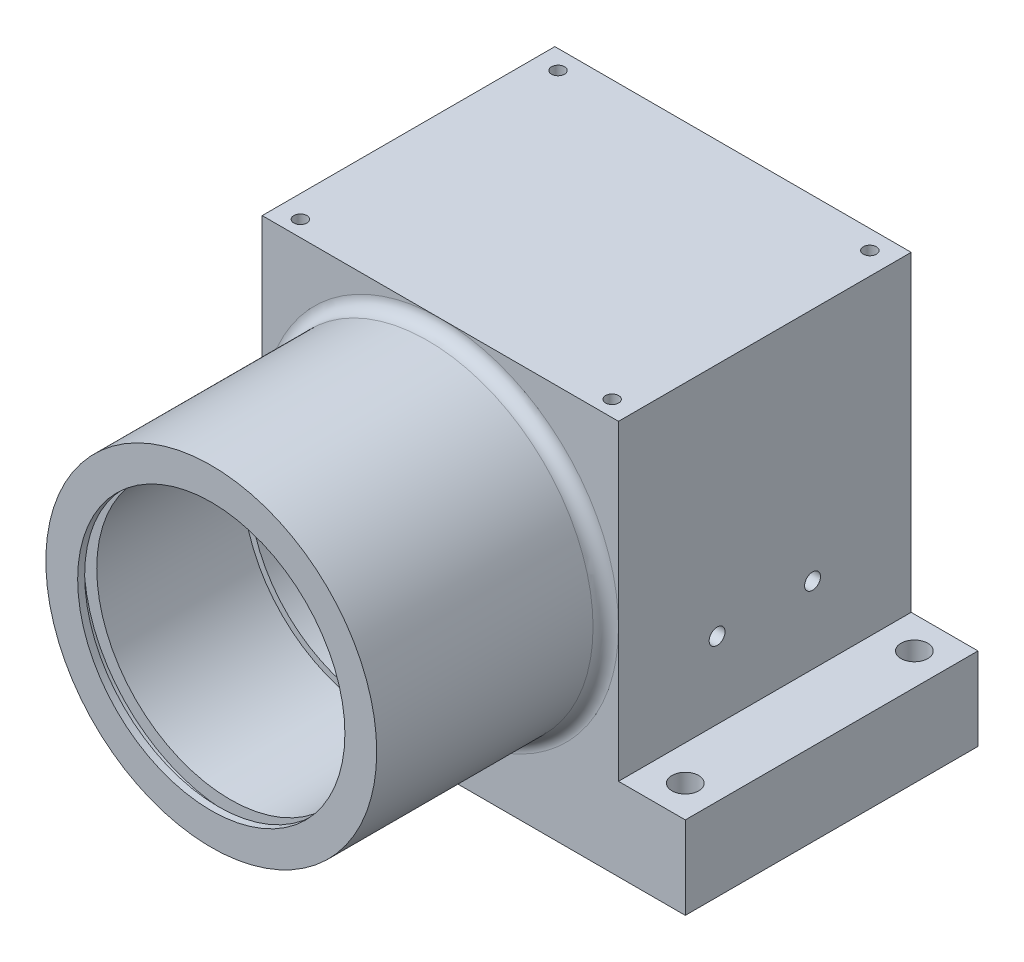
SolidWorks part; units mm, degrees
material "1060 合金"
ref_plane "前视基准面" through (0, 0, 0) normal (0, 0, 1) x (1, 0, 0)
ref_plane "上视基准面" through (0, 0, 0) normal (0, 1, 0) x (1, 0, 0)
ref_plane "右视基准面" through (0, 0, 0) normal (1, 0, 0) x (0, 0, -1)
sketch "草图1" plane through (0, 0, 0) normal (0, 0, 1) x (1, 0, 0)
  line L0 (0, -34) -> (0, 33.0223) construction
  line L1 (-28, -34) -> (28, -34)
  line L2 (-28, -34) -> (-28, 28)
  line L3 (-28, 28) -> (28, 28)
  line L4 (28, -34) -> (28, 28)
  line L5 (0, 0) -> (56.6994, 0) construction
  circle A0 centre (0, 0) radius 24 construction
  point P9 (0, 24)
  point P10 (0, -24)
  point P12 (24, 0)
  dimension "D1" = 10
  dimension "D2" = 48
  dimension "D3" = 4
  dimension "D4" = 4
extrude "凸台-拉伸1" add sketch "草图1" along normal blind 82
sketch "草图3" plane through (0, 0, 0) normal (1, 0, 0) x (0, 0, -1)
  line L0 (5.7193, 0) -> (-112.2198, 0) construction
  line L1 (0, -34) -> (0, 28) construction
  line L2 (-82, 0) -> (0, 0)
  line L3 (-82, 28) -> (-82, -34) construction
  line L4 (-82, 21) -> (-56, 21)
  line L5 (0, 0) -> (0, 23)
  line L7 (-52, 23) -> (0, 23)
  line L9 (-56, 21) -> (-56, 20)
  line L10 (-56, 20) -> (-52, 20)
  line L11 (-52, 23) -> (-52, 20)
  line L12 (-82, 0) -> (-82, 21)
  dimension "D1" = 20
  dimension "D2" = 21
  dimension "D3" = 4
  dimension "D4" = 23
  dimension "D5" = 26
revolve "切除-旋转2" cut sketch "草图3" angle 360 about L0
sketch "草图4" plane through (0, 0, 82) normal (0, 0, 1) x (1, 0, 0)
  line L0 (28, 28) -> (-28, 28) construction
  line L1 (-28, 28) -> (-28, -34) construction
  line L2 (-28, -34) -> (28, -34) construction
  line L3 (28, -34) -> (28, 28) construction
  line L4 (28, 28) -> (-28, 28)
  line L5 (-28, 28) -> (-28, -34)
  line L6 (-28, -34) -> (28, -34)
  line L7 (28, -34) -> (28, 28)
  circle A2 centre (0, 0) radius 26
  dimension "D1" = 52
chamfer "倒角1" [suppressed] distance 15 angle 45
extrude "切除-拉伸1" cut sketch "草图4" against normal blind 36
hole_wizard "M4 螺纹孔1" positions "草图12" profile "草图11" tap size "M4" standard "GB"
sketch "草图12" plane through (0, 0, 0) normal (0, 0, -1) x (-1, 0, 0)
  line L0 (0, 0) -> (0, 40.8365) construction
  line L11 (0, 0) -> (18.3848, 18.3848) construction
  circle A3 centre (0, 0) radius 26
  circle A4 centre (0, 0) radius 26 construction
  point P0 (18.3848, 18.3848)
  point P116 (18.3848, -18.3848)
  point P117 (-18.3848, -18.3848)
  point P118 (-18.3848, 18.3848)
  dimension "D1" = 45
  dimension "D2" = 4
  dimension "D3" = 3
sketch "草图11" plane through (-18.3848, 18.3848, 0) normal (1, 0, 0) x (0, 1, 0)
  line L0 (0, 0) -> (0, 11.0914)
  line L1 (0, 11.0914) -> (1.65, 10.1)
  line L2 (1.65, 10.1) -> (1.65, 0)
  line L5 (1.65, 0) -> (0, 0)
  line L10 (0, 11.0914) -> (-1.65, 10.1) construction
  line L11 (0, -6.35) -> (0, 107.95) construction
  dimension "螺纹孔钻头直径" = 3.3
  dimension "螺纹孔钻头深度" = 10.1
  dimension "导头角度" = 118
cosmetic thread "孔螺蚊线5" parameters "D1"=8, "D2"=4
cosmetic thread "孔螺蚊线6" parameters "D1"=8, "D2"=4
cosmetic thread "孔螺蚊线7" parameters "D1"=8, "D2"=4
cosmetic thread "孔螺蚊线8" parameters "D1"=8, "D2"=4
sketch "草图15" plane through (0, 0, 0) normal (0, 1, 0) x (1, 0, 0)
  line L0 (0, 0) -> (0, -98.0138) construction
  line L1 (-26, -82) -> (26, -82) construction
  line L2 (0, -80.9) -> (-23, -80.9)
  line L3 (0, -80.9) -> (0, -79)
  line L4 (0, -79) -> (-23, -79)
  line L5 (-23, -80.9) -> (-23, -79)
  dimension "D1" = 23
  dimension "D2" = 3
  dimension "D3" = 1.9
revolve "切除-旋转3" cut sketch "草图15" angle 360 about L0
fillet "圆角1" radius 2 1 edges at (26, 0, 46)
chamfer "倒角2" distance 1 angle 45 1 edges at (-23, 0, 0)
hole_wizard "M2.5 螺纹孔1" positions "草图18" profile "草图17" tap size "M2.5" standard "GB"
sketch "草图18" plane through (0, 28, 0) normal (0, 1, 0) x (1, 0, 0)
  line L0 (0, 0) -> (0, -42.6299) construction
  line L3 (-24.5, -43.5) -> (24.5, -43.5) construction
  line L4 (-24.5, -43.5) -> (-24.5, -3) construction
  line L5 (-24.5, -3) -> (24.5, -3) construction
  line L6 (24.5, -43.5) -> (24.5, -3) construction
  line L7 (-24.5, -43.5) -> (24.5, -3) construction
  line L8 (-24.5, -3) -> (24.5, -43.5) construction
  line L9 (28, 0) -> (-28, 0) construction
  point P7 (24.5, -3)
  point P92 (-24.5, -43.5)
  point P93 (-24.5, -3)
  point P94 (24.5, -43.5)
  dimension "D1" = 49
  dimension "D2" = 40.5
  dimension "D3" = 3
sketch "草图17" plane through (24.5, 28, 3) normal (1, 0, 0) x (0, 0, 1)
  line L0 (0, 0) -> (0, 7.8659)
  line L1 (0, 7.8659) -> (1.025, 7.25)
  line L2 (1.025, 7.25) -> (1.025, 0)
  line L5 (1.025, 0) -> (0, 0)
  line L10 (0, 7.8659) -> (-1.025, 7.25) construction
  line L11 (0, -6.35) -> (0, 107.95) construction
  dimension "螺纹孔钻头直径" = 2.05
  dimension "螺纹孔钻头深度" = 7.25
  dimension "导头角度" = 118
cosmetic thread "孔螺蚊线9" parameters "D1"=5, "D2"=2.5
cosmetic thread "孔螺蚊线10" parameters "D1"=5, "D2"=2.5
cosmetic thread "孔螺蚊线11" parameters "D1"=5, "D2"=2.5
cosmetic thread "孔螺蚊线12" parameters "D1"=5, "D2"=2.5
sketch "草图19" plane through (0, -34, 0) normal (0, -1, 0) x (1, 0, 0)
  line L0 (-28, 0) -> (28, 0) construction
  line L1 (-38.5, 0) -> (38.5, 0)
  line L2 (-38.5, 0) -> (-38.5, 46)
  line L3 (-38.5, 46) -> (38.5, 46)
  line L4 (38.5, 0) -> (38.5, 46)
  line L5 (-38.5, 0) -> (38.5, 46) construction
  line L6 (-38.5, 46) -> (38.5, 0) construction
  line L7 (28, 46) -> (28, 0) construction
  line L8 (28, 46) -> (-28, 46) construction
  point P0 (0, 23)
  line M2 (-28, 46) -> (-28, 0)
  line M4 (28, 0) -> (28, 46)
  dimension "D1" = 10.5
extrude "凸台-拉伸2" add sketch "草图19" against normal blind 13 contours L1 L4 L3 M4 | L3 L2 L1 M2 region at (-33.25, -34, 23) region at (33.25, -34, 23)
hole_wizard "M5 螺纹孔1" positions "草图21" profile "草图20" tap size "M5" standard "GB" end condition up to next
sketch "草图21" plane through (0, -34, 0) normal (0, -1, 0) x (-1, 0, 0)
  line L1 (-33.5, -41) -> (33.5, -41) construction
  line L2 (-33.5, -41) -> (-33.5, -5) construction
  line L3 (-33.5, -5) -> (33.5, -5) construction
  line L4 (33.5, -41) -> (33.5, -5) construction
  line L5 (-33.5, -41) -> (33.5, -5) construction
  line L6 (-33.5, -5) -> (33.5, -41) construction
  line L7 (0, 0) -> (0, -56.3467) construction
  line L9 (38.5, -46) -> (-38.5, -46) construction
  line L10 (38.5, 0) -> (-38.5, 0) construction
  point P3 (33.5, -5)
  point P78 (-33.5, -41)
  point P79 (-33.5, -5)
  point P80 (33.5, -41)
  dimension "D1" = 67
  dimension "D2" = 5
  dimension "D3" = 5
sketch "草图20" plane through (-33.5, -34, 5) normal (1, 0, 0) x (0, 0, -1)
  line L0 (0, 0) -> (0, 13)
  line L1 (0, 13) -> (2.1, 13)
  line L2 (2.1, 13) -> (2.1, 0)
  line L5 (2.1, 0) -> (0, 0)
  line L11 (0, -6.35) -> (0, 107.95) construction
  dimension "通孔螺纹孔钻头直径" = 4.2
  dimension "通孔螺纹孔钻头深度" = 13
cosmetic thread "孔螺蚊线13" parameters "D2"=5
cosmetic thread "孔螺蚊线14" parameters "D2"=5
cosmetic thread "孔螺蚊线15" parameters "D2"=5
cosmetic thread "孔螺蚊线16" parameters "D2"=5
hole_wizard "M3 螺纹孔1" positions "草图23" profile "草图24" tap size "M3" standard "GB"
sketch "草图23" plane through (28, 0, 0) normal (1, 0, 0) x (0, 0, -1)
  line L0 (-23, 28) -> (-23, -39.4535) construction
  line L1 (-46, 28) -> (0, 28) construction
  line L3 (0, -34) -> (-46, -34) construction
  point P0 (-30.5, -9)
  point P2 (-15.5, -9)
  dimension "D1" = 15
  dimension "D2" = 25
sketch "草图24" plane through (28, -9, 30.5) normal (0, 1, 0) x (0, 0, -1)
  line L0 (0, 0) -> (0, 6.2511)
  line L1 (0, 6.2511) -> (1.25, 5.5)
  line L2 (1.25, 5.5) -> (1.25, 0)
  line L5 (1.25, 0) -> (0, 0)
  line L10 (0, 6.2511) -> (-1.25, 5.5) construction
  line L11 (0, -6.35) -> (0, 107.95) construction
  dimension "螺纹孔钻头直径" = 2.5
  dimension "螺纹孔钻头深度" = 5.5
  dimension "导头角度" = 118
cosmetic thread "孔螺蚊线17" parameters "D1"=5.5, "D2"=3
cosmetic thread "孔螺蚊线18" parameters "D1"=5.5, "D2"=3
mirror "镜向1" about plane through (0, 0, 0) normal (1, 0, 0) of "M3 螺纹孔1"
